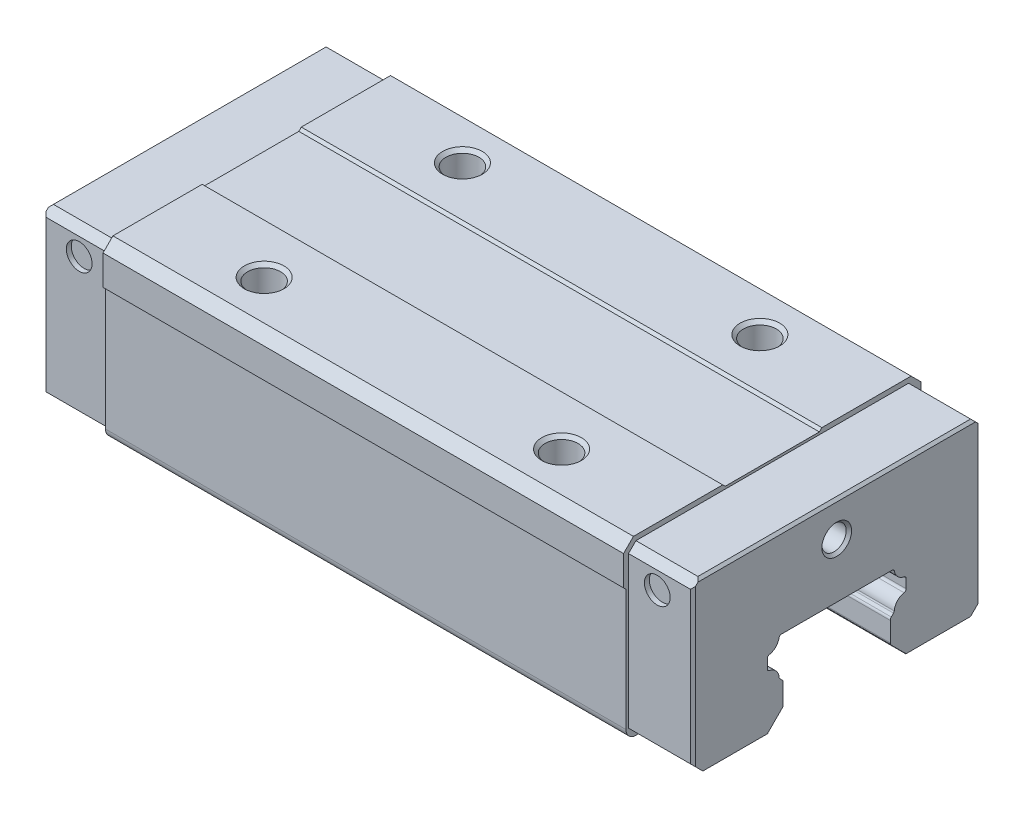
SolidWorks part; units mm, degrees
ref_plane "Front Plane" through (0, 0, 0) normal (0, 0, 1) x (1, 0, 0)
ref_plane "Top Plane" through (0, 0, 0) normal (0, 1, 0) x (1, 0, 0)
ref_plane "Right Plane" through (0, 0, 0) normal (1, 0, 0) x (0, 0, -1)
ref_plane "Plane1" through (0, 0, 0) normal (1, 0, 0) x (0, 0, -1)
sketch "Sketch1" plane through (0, 0, 0) normal (1, 0, 0) x (0, 0, -1)
  line L0 (-30, 33) -> (-30, 27)
  line L1 (-30, 27) -> (-29.5, 26.5)
  line L2 (-29.5, 26.5) -> (-29.5, 2)
  line L3 (-27.5, 0) -> (27.5, 0)
  line L4 (29.5, 2) -> (29.5, 26.5)
  line L5 (29.5, 26.5) -> (30, 27)
  line L6 (30, 27) -> (30, 33)
  line L7 (30, 33) -> (28, 35)
  line L8 (28, 35) -> (10, 35)
  line L9 (10, 35) -> (9.5, 34.5)
  line L10 (9.5, 34.5) -> (-9.5, 34.5)
  line L11 (-9.5, 34.5) -> (-10, 35)
  line L12 (-10, 35) -> (-28, 35)
  line L13 (-28, 35) -> (-30, 33)
  arc A0 (-29.5, 2) -> (-27.5, 0) centre (-27.5, 2) ccw
  arc A1 (27.5, 0) -> (29.5, 2) centre (27.5, 2) ccw
extrude "Boss-Extrude1" add sketch "Sketch1" against normal blind 52.5 and the other way blind 52.5
ref_plane "Plane2" through (-65.5, 0, 0) normal (1, 0, 0) x (0, 0, -1)
sketch "Sketch2" plane through (-65.5, 0, 0) normal (1, 0, 0) x (0, 0, -1)
  line L0 (-29, 2) -> (-27, 0)
  line L1 (-27, 0) -> (27, 0)
  line L2 (27, 0) -> (29, 2)
  line L3 (29, 2) -> (29, 32.5)
  line L4 (29, 32.5) -> (27.5, 34)
  line L5 (27.5, 34) -> (-27.5, 34)
  line L6 (-27.5, 34) -> (-29, 32.5)
  line L7 (-29, 32.5) -> (-29, 2)
extrude "Boss-Extrude2" add sketch "Sketch2" along normal blind 13
ref_plane "Plane3" through (65.5, 0, 0) normal (1, 0, 0) x (0, 0, -1)
sketch "Sketch3" plane through (65.5, 0, 0) normal (1, 0, 0) x (0, 0, -1)
  line L0 (-29, 2) -> (-27, 0)
  line L1 (-27, 0) -> (27, 0)
  line L2 (27, 0) -> (29, 2)
  line L3 (29, 2) -> (29, 32.5)
  line L4 (29, 32.5) -> (27.5, 34)
  line L5 (27.5, 34) -> (-27.5, 34)
  line L6 (-27.5, 34) -> (-29, 32.5)
  line L7 (-29, 32.5) -> (-29, 2)
extrude "Boss-Extrude3" add sketch "Sketch3" against normal blind 13
ref_plane "Plane4" through (0, 0, 0) normal (1, 0, 0) x (0, 0, -1)
sketch "Sketch4" plane through (0, 0, 0) normal (1, 0, 0) x (0, 0, -1)
  line L0 (-14, 13.1484) -> (-14, 11.3516)
  line L1 (-11.4582, 8.3602) -> (-11.005, 7.907)
  line L2 (-10.8, 7.4121) -> (-10.8, 3.4908)
  line L3 (-11.0056, 2.9944) -> (-13.7956, 0.2044)
  line L4 (-14, -0.2891) -> (-14, -5.5)
  line L5 (-14, -5.5) -> (-12.5, -7)
  line L6 (-12.5, -7) -> (-5, -7)
  line L7 (-5, -7) -> (-4.5, -6.5)
  line L8 (-4.5, -6.5) -> (4.5, -6.5)
  line L9 (4.5, -6.5) -> (5, -7)
  line L10 (5, -7) -> (12.5, -7)
  line L11 (12.5, -7) -> (14, -5.5)
  line L12 (14, -5.5) -> (14, -0.2891)
  line L13 (13.7956, 0.2044) -> (11.0056, 2.9944)
  line L14 (10.8, 3.4908) -> (10.8, 7.4121)
  line L15 (11.005, 7.907) -> (11.4582, 8.3602)
  line L16 (14, 11.3516) -> (14, 13.1484)
  line L17 (11.147, 16) -> (-11.147, 16)
  arc A0 (-13.5924, 13.6398) -> (-14, 13.1484) centre (-13.5072, 13.1544) ccw
  arc A1 (-14, 11.3516) -> (-13.5924, 10.8602) centre (-13.5025, 11.3495) ccw
  arc A2 (-13.5924, 10.8602) -> (-11.6026, 8.669) centre (-14.042, 8.4529) cw
  arc A3 (-11.6026, 8.669) -> (-11.4582, 8.3602) centre (-11.1281, 8.7028) ccw
  arc A4 (-11.005, 7.907) -> (-10.8, 7.4121) centre (-11.4843, 7.4185) cw
  arc A5 (-10.8, 3.4908) -> (-11.0056, 2.9944) centre (-11.5021, 3.4908) cw
  arc A6 (-13.7956, 0.2044) -> (-14, -0.2891) centre (-13.302, -0.2891) ccw
  arc A7 (14, -0.2891) -> (13.7956, 0.2044) centre (13.302, -0.2891) ccw
  arc A8 (11.0056, 2.9944) -> (10.8, 3.4908) centre (11.5021, 3.4908) cw
  arc A9 (10.8, 7.4121) -> (11.005, 7.907) centre (11.4843, 7.4185) cw
  arc A10 (11.4582, 8.3602) -> (11.6026, 8.669) centre (11.1281, 8.7028) ccw
  arc A11 (11.6026, 8.669) -> (13.5924, 10.8602) centre (14.042, 8.4529) cw
  arc A12 (13.5924, 10.8602) -> (14, 11.3516) centre (13.5025, 11.3495) ccw
  arc A13 (14, 13.1484) -> (13.5924, 13.6398) centre (13.5072, 13.1544) ccw
  arc A14 (13.5924, 13.6398) -> (11.6358, 15.5932) centre (14.0457, 16.0505) cw
  arc A15 (11.6358, 15.5932) -> (11.147, 16) centre (11.1545, 15.512) ccw
  arc A16 (-11.147, 16) -> (-11.6358, 15.5932) centre (-11.1545, 15.512) ccw
  arc A17 (-11.6358, 15.5932) -> (-13.5924, 13.6398) centre (-14.0457, 16.0505) cw
extrude "Cut-Extrude1" cut sketch "Sketch4" against normal blind 65.5 and the other way blind 65.5
ref_plane "Plane5" through (0, 0, 0) normal (0, 0, 1) x (1, 0, 0)
sketch "Sketch5" plane through (0, 0, 0) normal (0, 0, 1) x (1, 0, 0)
  line L0 (-65.5, 33.5) -> (-65, 34)
  line L1 (-65, 34) -> (-65.5, 34)
  line L2 (-65.5, 34) -> (-65.5, 33.5)
extrude "Cut-Extrude2" cut sketch "Sketch5" against normal blind 29 and the other way blind 29
ref_plane "Plane6" through (0, 0, 0) normal (0, 0, 1) x (1, 0, 0)
sketch "Sketch6" plane through (0, 0, 0) normal (0, 0, 1) x (1, 0, 0)
  line L0 (65, 34) -> (65.5, 33.5)
  line L1 (65.5, 33.5) -> (65.5, 34)
  line L2 (65.5, 34) -> (65, 34)
extrude "Cut-Extrude3" cut sketch "Sketch6" against normal blind 29 and the other way blind 29
ref_plane "Plane7" through (0, 0, 29) normal (0, 0, 1) x (1, 0, 0)
sketch "Sketch7" plane through (0, 0, 29) normal (0, 0, 1) x (1, 0, 0)
  circle A0 centre (58.3, 29) radius 2.6
extrude "Cut-Extrude4" cut sketch "Sketch7" against normal blind 1
ref_plane "Plane8" through (0, 0, 29) normal (0, 0, 1) x (1, 0, 0)
sketch "Sketch8" plane through (0, 0, 29) normal (0, 0, 1) x (1, 0, 0)
  circle A0 centre (-58.3, 29) radius 2.6
extrude "Cut-Extrude5" cut sketch "Sketch8" against normal blind 1
ref_plane "Plane9" through (0, 0, -29) normal (0, 0, 1) x (1, 0, 0)
sketch "Sketch9" plane through (0, 0, -29) normal (0, 0, 1) x (1, 0, 0)
  circle A0 centre (58.3, 29) radius 2.6
extrude "Cut-Extrude6" cut sketch "Sketch9" along normal blind 1
ref_plane "Plane10" through (0, 0, -29) normal (0, 0, 1) x (1, 0, 0)
sketch "Sketch10" plane through (0, 0, -29) normal (0, 0, 1) x (1, 0, 0)
  circle A0 centre (-58.3, 29) radius 2.6
extrude "Cut-Extrude7" cut sketch "Sketch10" along normal blind 1
ref_plane "Plane11" through (0, 0, 0) normal (0, 0, 1) x (1, 0, 0)
sketch "Sketch11" plane through (0, 0, 0) normal (0, 0, 1) x (1, 0, 0)
  line L0 (-65.5, 27) -> (-65.5, 30)
  line L1 (-65.5, 30) -> (-64.9585, 29.4585)
  line L2 (-64.9585, 29.4585) -> (-59.5, 29.4585)
  line L3 (-59.5, 29.4585) -> (-58.0806, 27)
  line L4 (-58.0806, 27) -> (-65.5, 27)
  line L5 (-58.0806, 27) -> (-65.5, 27) construction
revolve "Cut-Revolve1" cut sketch "Sketch11" angle 360 about L5 reverse direction yes
cosmetic thread "Cosmetic Thread1" parameters "D1"=5, "D2"=6
ref_plane "Plane12" through (0, 0, 0) normal (0, 0, 1) x (1, 0, 0)
sketch "Sketch12" plane through (0, 0, 0) normal (0, 0, 1) x (1, 0, 0)
  line L0 (58.0806, 27) -> (59.5, 29.4585)
  line L1 (59.5, 29.4585) -> (64.9585, 29.4585)
  line L2 (64.9585, 29.4585) -> (65.5, 30)
  line L3 (65.5, 30) -> (65.5, 27)
  line L4 (65.5, 27) -> (58.0806, 27)
  line L5 (65.5, 27) -> (58.0806, 27) construction
revolve "Cut-Revolve2" cut sketch "Sketch12" angle 360 about L5 reverse direction yes
cosmetic thread "Cosmetic Thread2" parameters "D1"=5, "D2"=6
ref_plane "Plane13" through (0, 0, 20) normal (0, 0, 1) x (1, 0, 0)
sketch "Sketch13" plane through (0, 0, 20) normal (0, 0, 1) x (1, 0, 0)
  line L0 (-30, 35) -> (-26, 35)
  line L1 (-26, 35) -> (-26.6765, 34.3235)
  line L2 (-26.6765, 34.3235) -> (-26.6765, 25.4)
  line L3 (-26.6765, 25.4) -> (-30, 23.4812)
  line L4 (-30, 23.4812) -> (-30, 35)
  line L5 (-30, 23.4812) -> (-30, 35) construction
revolve "Cut-Revolve3" cut sketch "Sketch13" angle 360 about L5 reverse direction yes
cosmetic thread "Cosmetic Thread3" parameters "D1"=8, "D2"=8
ref_plane "Plane14" through (0, 0, 20) normal (0, 0, 1) x (1, 0, 0)
sketch "Sketch14" plane through (0, 0, 20) normal (0, 0, 1) x (1, 0, 0)
  line L0 (30, 35) -> (34, 35)
  line L1 (34, 35) -> (33.3235, 34.3235)
  line L2 (33.3235, 34.3235) -> (33.3235, 25.4)
  line L3 (33.3235, 25.4) -> (30, 23.4812)
  line L4 (30, 23.4812) -> (30, 35)
  line L5 (30, 23.4812) -> (30, 35) construction
revolve "Cut-Revolve4" cut sketch "Sketch14" angle 360 about L5 reverse direction yes
cosmetic thread "Cosmetic Thread4" parameters "D1"=8, "D2"=8
ref_plane "Plane15" through (0, 0, -20) normal (0, 0, 1) x (1, 0, 0)
sketch "Sketch15" plane through (0, 0, -20) normal (0, 0, 1) x (1, 0, 0)
  line L0 (-30, 35) -> (-26, 35)
  line L1 (-26, 35) -> (-26.6765, 34.3235)
  line L2 (-26.6765, 34.3235) -> (-26.6765, 25.4)
  line L3 (-26.6765, 25.4) -> (-30, 23.4812)
  line L4 (-30, 23.4812) -> (-30, 35)
  line L5 (-30, 23.4812) -> (-30, 35) construction
revolve "Cut-Revolve5" cut sketch "Sketch15" angle 360 about L5 reverse direction yes
cosmetic thread "Cosmetic Thread5" parameters "D1"=8, "D2"=8
ref_plane "Plane16" through (0, 0, -20) normal (0, 0, 1) x (1, 0, 0)
sketch "Sketch16" plane through (0, 0, -20) normal (0, 0, 1) x (1, 0, 0)
  line L0 (30, 35) -> (34, 35)
  line L1 (34, 35) -> (33.3235, 34.3235)
  line L2 (33.3235, 34.3235) -> (33.3235, 25.4)
  line L3 (33.3235, 25.4) -> (30, 23.4812)
  line L4 (30, 23.4812) -> (30, 35)
  line L5 (30, 23.4812) -> (30, 35) construction
revolve "Cut-Revolve6" cut sketch "Sketch16" angle 360 about L5 reverse direction yes
cosmetic thread "Cosmetic Thread6" parameters "D1"=8, "D2"=8
ref_plane "Plane17" through (0, 0, 0) normal (0, 1, 0) x (1, 0, 0)
sketch "Sketch17" plane through (0, 0, 0) normal (0, 1, 0) x (1, 0, 0)
  line L0 (-130.5, 29.5) -> (-130.5, -29.5)
  line L1 (-130.5, -29.5) -> (-65, -29.5)
  line L2 (-65, -29.5) -> (-65, -29)
  line L3 (-65, -29) -> (-65.5, -28.5)
  line L4 (-65.5, -28.5) -> (-65.5, -29)
  line L5 (-65.5, -29) -> (-130, -29)
  line L6 (-130, -29) -> (-130, 29)
  line L7 (-130, 29) -> (-65.5, 29)
  line L8 (-65.5, 29) -> (-65.5, 28.5)
  line L9 (-65.5, 28.5) -> (-65, 29)
  line L10 (-65, 29) -> (-65, 29.5)
  line L11 (-65, 29.5) -> (-130.5, 29.5)
extrude "Cut-Extrude8" cut sketch "Sketch17" along normal blind 35
ref_plane "Plane18" through (0, 0, 0) normal (0, 1, 0) x (1, 0, 0)
sketch "Sketch18" plane through (0, 0, 0) normal (0, 1, 0) x (1, 0, 0)
  line L0 (65, -29) -> (65, -29.5)
  line L1 (65, -29.5) -> (130.5, -29.5)
  line L2 (130.5, -29.5) -> (130.5, 29.5)
  line L3 (130.5, 29.5) -> (65, 29.5)
  line L4 (65, 29.5) -> (65, 29)
  line L5 (65, 29) -> (65.5, 28.5)
  line L6 (65.5, 28.5) -> (65.5, 29)
  line L7 (65.5, 29) -> (130, 29)
  line L8 (130, 29) -> (130, -29)
  line L9 (130, -29) -> (65.5, -29)
  line L10 (65.5, -29) -> (65.5, -28.5)
  line L11 (65.5, -28.5) -> (65, -29)
extrude "Cut-Extrude9" cut sketch "Sketch18" along normal blind 35
